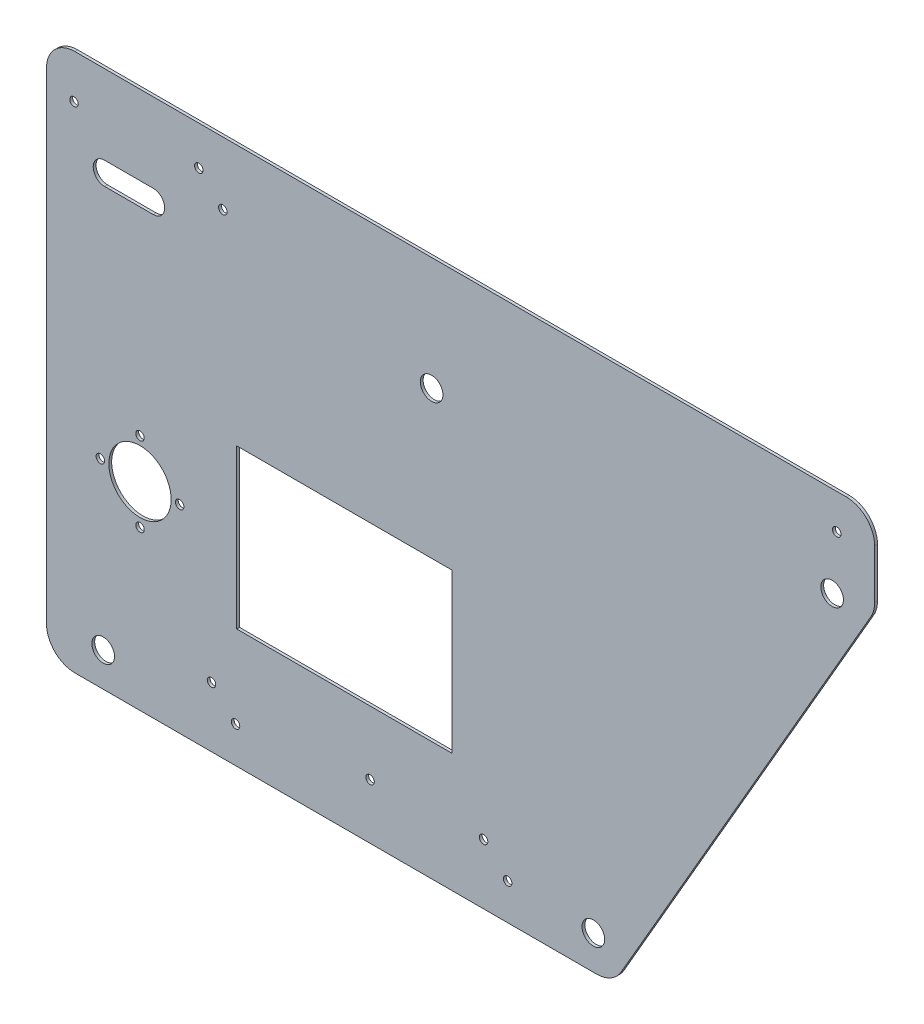
SolidWorks part; units mm, degrees
ref_plane "Front Plane" through (0, 0, 0) normal (0, 0, 1) x (1, 0, 0)
ref_plane "Top Plane" through (0, 0, 0) normal (0, 1, 0) x (1, 0, 0)
ref_plane "Right Plane" through (0, 0, 0) normal (1, 0, 0) x (0, 0, -1)
sketch "Sketch1" plane through (0, 0, 0) normal (0, 0, 1) x (1, 0, 0)
  line L0 (100, 80) -> (192.376, 80)
  line L1 (-100, -80) -> (100, -80)
  line L2 (-100, -80) -> (-100, 80)
  line L3 (-100, 80) -> (100, 80)
  line L4 (100, -80) -> (100, 80)
  line L5 (-100, -80) -> (100, 80) construction
  line L6 (-100, 80) -> (100, -80) construction
  line L7 (192.376, 80) -> (100, -80)
  line L8 (100, 80) -> (100, -80)
  line L10 (-100, 80) -> (192.376, 80)
  line L11 (-100, 80) -> (-100, 110)
  line L12 (-100, 110) -> (192.376, 110)
  line L13 (192.376, 80) -> (192.376, 110)
  point P0 (0, 0)
  dimension "D1" = 160
  dimension "D2" = 200
  dimension "D3" = 30
  dimension "D4" = 30
extrude "Boss-Extrude1" add sketch "Sketch1" along normal blind 1 contours L1 L4 L3 L2 | L7 L0 L4 | L11 L10 L13 L12 region at (0, 0, 0) region at (130.792, 26.6667, 0)
fillet "Fillet1" radius 10 5 edges at (100, -80, 0.5) (-100, -80, 0.5) (192.376, 110, 0.5) (-100, 110, 0.5) (192.376, 80, 0.5)
sketch "Sketch2" plane through (0, 0, 1) normal (0, 0, 1) x (1, 0, 0)
  line L0 (-90, -80) -> (94.2265, -80) construction
  line L1 (191.0363, 77.6795) -> (102.8868, -75) construction
  line L2 (-100, -70) -> (-100, 100) construction
  line L3 (-90, 110) -> (182.376, 110) construction
  line L4 (-79.5166, 78) -> (-62.3003, 78) construction
  line L7 (-100, -70) -> (-100, 100) construction
  line L8 (-29.8584, 15) -> (-29.8584, -35) construction
  line L9 (-79.5166, 82) -> (-62.3003, 82)
  line L10 (-79.5166, 74) -> (-62.3003, 74)
  line L11 (-32.8584, 18) -> (43.1416, 18)
  line L12 (-32.8584, 18) -> (-32.8584, -38)
  line L13 (-32.8584, -38) -> (43.1416, -38)
  line L14 (43.1416, 18) -> (43.1416, -38)
  line L15 (20.1416, 15) -> (-29.8584, 15) construction
  line L16 (-32.5193, -35) -> (42.4807, -35) construction
  line L17 (40.1416, -35) -> (40.1416, 15) construction
  circle A0 centre (93.0718, -68) radius 4
  circle A1 centre (177.3649, 78) radius 4
  circle A2 centre (-67, -10) radius 11
  circle A3 centre (-80, -68) radius 4
  circle A4 centre (-53, -10) radius 1.5
  circle A5 centre (-67, 4) radius 1.5
  circle A6 centre (-81, -10) radius 1.5
  circle A7 centre (-67, -24) radius 1.5
  circle A10 centre (35.9573, 70) radius 4
  arc A11 (-79.5166, 82) -> (-79.5166, 74) centre (-79.5166, 78) ccw
  arc A12 (-62.3003, 74) -> (-62.3003, 82) centre (-62.3003, 78) ccw
  circle A32 centre (62.7961, -67.2426) radius 1.5
  circle A33 centre (54.3108, -58.7574) radius 1.5
  circle A34 centre (-33.2742, -67.2426) radius 1.5
  circle A35 centre (-41.7595, -58.7574) radius 1.5
  circle A36 centre (14.2259, -60.5) radius 1.5
  circle A37 centre (-37.7547, 87.7574) radius 1.5
  circle A38 centre (-46.24, 96.2426) radius 1.5
  circle A39 centre (-90.2956, 94.5) radius 1.5
  circle A40 centre (178.9933, 97.6095) radius 1.5
  point P12 (-70.9085, 78)
  dimension "D3" = 8
  dimension "D4" = 8
  dimension "D9" = 22
  dimension "D10" = 8
  dimension "D12" = 3
  dimension "D13" = 3
  dimension "D14" = 3
  dimension "D15" = 3
  dimension "D16" = 14
  dimension "D20" = 4
  dimension "D22" = 8
  dimension "D23" = 3
  dimension "D24" = 20
  dimension "D25" = 3
  dimension "D1" = 12
  dimension "D2" = 12
  dimension "D5" = 32
  dimension "D6" = 12
  dimension "D7" = 33
  dimension "D8" = 70
  dimension "D11" = 12
  dimension "D17" = 14
  dimension "D18" = 14
  dimension "D19" = 14
  dimension "D21" = 40
  dimension "D26" = 3
  dimension "D27" = 3
  dimension "D28" = 3
  dimension "D29" = 3
extrude "Cut-Extrude1" cut sketch "Sketch2" against normal blind 3
